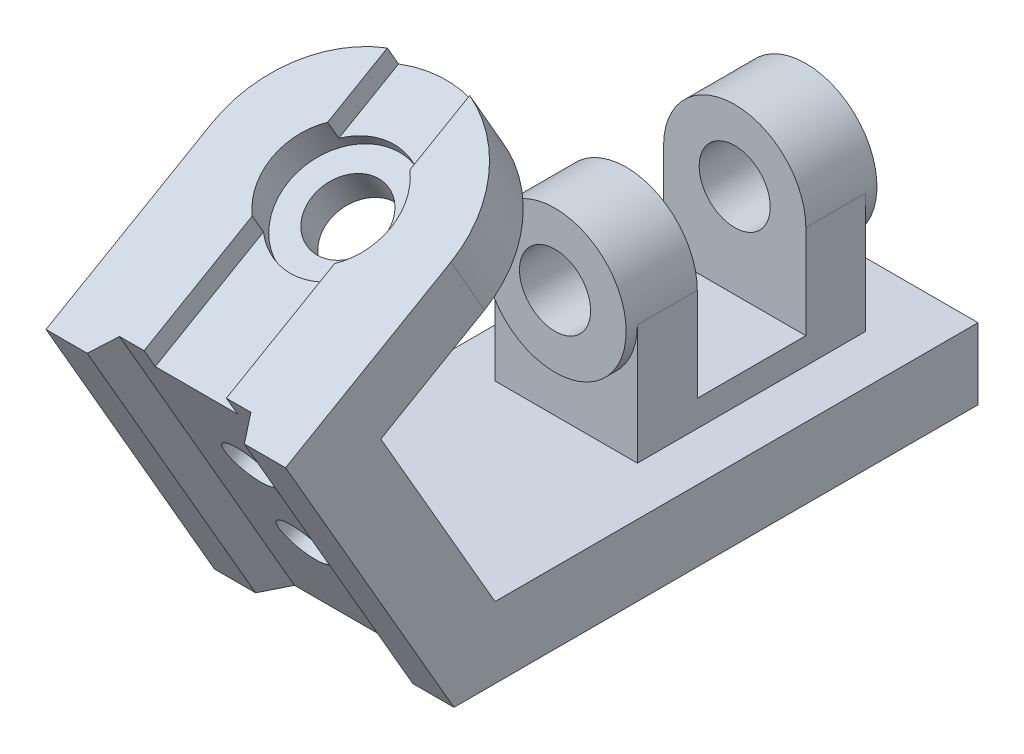
SolidWorks part; units mm, degrees
material "Gray Cast Iron"
ref_plane "Front Plane" through (0, 0, 0) normal (0, 0, 1) x (1, 0, 0)
ref_plane "Top Plane" through (0, 0, 0) normal (0, 1, 0) x (1, 0, 0)
ref_plane "Right Plane" through (0, 0, 0) normal (1, 0, 0) x (0, 0, -1)
sketch "Sketch1" plane through (0, 0, 0) normal (1, 0, 0) x (0, 0, -1)
  line L0 (0, 0) -> (140, 0)
  line L1 (140, 0) -> (140, 19)
  line L2 (140, 19) -> (10.9697, 19)
  line L3 (10.9697, 19) -> (-19.5455, 71.8538)
  line L4 (0, 0) -> (-45, 77.9423)
  line L5 (-45, 77.9423) -> (-0.8327, 103.4423)
  line L6 (-0.8327, 103.4423) -> (8.1673, 87.8538)
  line L7 (8.1673, 87.8538) -> (-19.5455, 71.8538)
  dimension "D1" = 140
  dimension "D2" = 19
  dimension "D3" = 19
  dimension "D4" = 90
  dimension "D5" = 51
  dimension "D6" = 18
  dimension "D7" = 60
extrude "Base" add sketch "Sketch1" along normal mid plane 64
sketch "Sketch2" plane through (0, 77.9423, 45) normal (0, 0.866, 0.5) x (1, 0, 0)
  line L0 (32, 51) -> (-32, 51) construction
  circle A0 centre (0, 51) radius 32
extrude "Boss-Extrude2" add sketch "Sketch2" against normal up to surface (18 mm away) contours A0 up to face at (0, 79.8538, 5.6891)
sketch "Sketch3" plane through (0, 77.9423, 45) normal (0, 0.866, 0.5) x (1, 0, 0)
  circle A0 centre (0, 51) radius 16
  circle A1 centre (0, 51) radius 9.5
  dimension "D1" = 19
  dimension "D2" = 32
extrude "Cut-Extrude1" cut sketch "Sketch3" against normal blind 9 contours A0 A1 | A1 region at (-15.5475, 103.4423, 0.8327) region at (0, 103.4423, 0.8327)
extrude "Cut-Extrude2" cut sketch "Sketch3<4>" against normal up to surface (18 mm away) contours A1 region at (0, 103.4423, 0.8327) up to face at (0, 83.8538, -1.2391)
sketch "Sketch3<4>" plane through (0, 77.9423, 45) normal (0, 0.866, 0.5) x (1, 0, 0) same geometry as "Sketch3"
sketch "Sketch5" plane through (0, 77.9423, 45) normal (0, 0.866, 0.5) x (1, 0, 0)
  line L0 (0, 0) -> (0, 83) construction
  line L1 (-17.5359, 6) -> (17.5359, 6)
  line L2 (17.5359, 6) -> (21, 0)
  line L3 (32, 0) -> (-32, 0) construction
  line L4 (21, 0) -> (21, 13.3713) construction
  line L5 (-21, 0) -> (-21, 13.3713) construction
  line L6 (-17.5359, 6) -> (-21, 0)
  line L7 (-21, 0) -> (-21, -1.7875)
  line L8 (-21, -1.7875) -> (21, -1.7875)
  line L9 (21, -1.7875) -> (21, 0)
  arc A0 (32, 51) -> (-32, 51) centre (0, 51) ccw construction
  point P14 (0, 6)
  dimension "D1" = 30
  dimension "D2" = 42
  dimension "D3" = 6
extrude "Cut-Extrude3" cut sketch "Sketch5" against normal through all contours L1 L2 L9 L8 L7 L6
sketch "Sketch6" plane through (0, 77.9423, 45) normal (0, 0.866, 0.5) x (1, 0, 0)
  line L0 (0, 6) -> (0, 83) construction
  line L1 (-17.5359, 6) -> (17.5359, 6) construction
  line L3 (-11, -8.5) -> (11, -8.5)
  line L4 (-11, -8.5) -> (-11, 91.5)
  line L5 (-11, 91.5) -> (11, 91.5)
  line L6 (11, -8.5) -> (11, 91.5)
  line L7 (-11, -8.5) -> (11, 91.5) construction
  line L8 (-11, 91.5) -> (11, -8.5) construction
  arc A0 (32, 51) -> (-32, 51) centre (0, 51) ccw construction
  circle A1 centre (0, 51) radius 9.5 construction
  point P7 (0, 41.5)
  dimension "D1" = 22
  dimension "D2" = 100
extrude "Cut-Extrude4" cut sketch "Sketch6" against normal blind 6
sketch "Sketch7" plane through (0, 3, -5.1962) normal (0, -0.5, 0.866) x (1, 0, 0)
  line L0 (0, 84) -> (0, -3.4641) construction
  line L1 (-11, 84) -> (11, 84) construction
  line L2 (-17.5359, -3.4641) -> (17.5359, -3.4641) construction
  circle A0 centre (0, 56) radius 6.5
  circle A1 centre (0, 27) radius 6.5
  dimension "D1" = 13
  dimension "D2" = 29
  dimension "D3" = 28
extrude "Cut-Extrude5" cut sketch "Sketch7" against normal up to surface (13 mm away) up to face at (0, 45.4269, 4.2879)
sketch "Sketch8" plane through (0, 19, 0) normal (0, 1, 0) x (1, 0, 0)
  line L0 (0, 140) -> (0, 45) construction
  line L1 (32, 140) -> (-32, 140) construction
  line L3 (-19, 62) -> (19, 62)
  line L4 (-19, 62) -> (-19, 123)
  line L5 (-19, 123) -> (19, 123)
  line L6 (19, 62) -> (19, 123)
  line L7 (-19, 62) -> (19, 123) construction
  line L8 (-19, 123) -> (19, 62) construction
  point P5 (0, 92.5)
  dimension "D1" = 17
  dimension "D2" = 38
  dimension "D3" = 61
extrude "Boss-Extrude4" add sketch "Sketch8" along normal blind 32
ref_plane "Plane1" through (0, 0, -92.5) normal (0, 0, -1) x (-1, 0, 0)
sketch "Sketch10" plane through (0, 0, -92.5) normal (0, 0, -1) x (-1, 0, 0)
  line L0 (-19, 51) -> (19, 51) construction
  circle A0 centre (0, 51) radius 19
extrude "Boss-Extrude5" add sketch "Sketch10" along normal mid plane 67
sketch "Sketch11" plane through (0, 0, -126) normal (0, 0, -1) x (-1, 0, 0)
  circle A0 centre (0, 51) radius 9.5
  dimension "D1" = 19
extrude "Cut-Extrude6" cut sketch "Sketch11" against normal up to surface (67 mm away) up to face at (0, 70, -59)
sketch "Sketch12" plane through (0, 0, 0) normal (1, 0, 0) x (0, 0, -1)
  line L0 (92.5, 19) -> (92.5, 107.0773) construction
  line L1 (78, 90.6078) -> (107, 90.6078)
  line L2 (78, 90.6078) -> (78, 26)
  line L3 (78, 26) -> (107, 26)
  line L4 (107, 90.6078) -> (107, 26)
  line L5 (62, 19) -> (123, 19) construction
  dimension "D1" = 7
  dimension "D2" = 29
extrude "Cut-Extrude8" cut sketch "Sketch12" against normal mid plane 67
